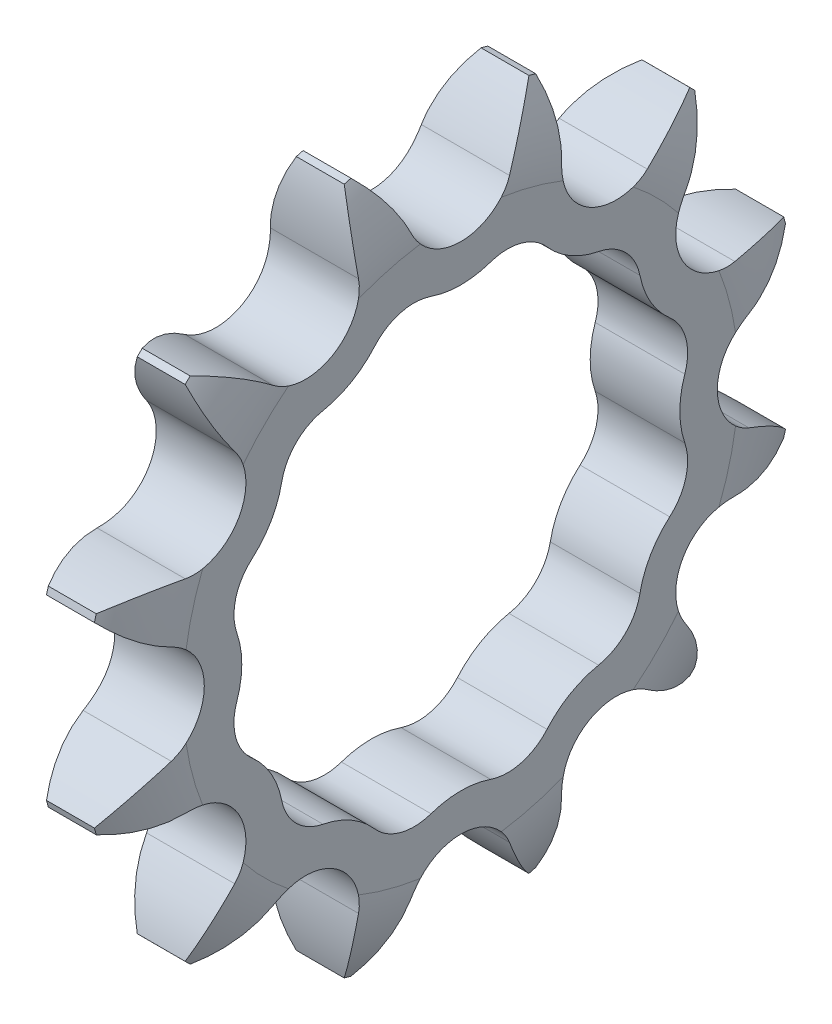
SolidWorks part; units mm, degrees
material "POM Acetal Copolymer"
ref_plane "Plane1" through (0, 0, 0) normal (0, 0, 1) x (1, 0, 0)
ref_plane "Plane2" through (0, 0, 0) normal (0, 1, 0) x (1, 0, 0)
ref_plane "Plane3" through (0, 0, 0) normal (1, 0, 0) x (0, 0, -1)
sketch "Clipboard" plane through (0, 0, 0) normal (0, 1, 0) x (1, 0, 0)
  line L0 (0, 0) -> (9.3169, -1.9804)
  line L1 (-15, 0) -> (100, 0) construction
  line L2 (0, 0) -> (-0.8203, 0.9272)
  line L3 (0, 0) -> (-8.8973, 3.4006)
  line L4 (0, 0) -> (3.0323, 0.6445)
  line L5 (0, 0) -> (-46.8476, -17.4728)
  line L6 (0, 0) -> (-4.4098, -2.9753)
  line L7 (-0.8203, 0.9272) -> (47.8986, 12.1748)
  line L8 (-76.2, 38.1) -> (-72.9, 38.1)
  line L9 (-73.3242, 40.7328) -> (-72.926, 40.7699)
  line L10 (-73.4529, 9.1872) -> (-63.2129, 9.1872)
  circle A0 centre (0, 0) radius 3.175
  circle A1 centre (0, 0) radius 13.0987
  circle A2 centre (0, 0) radius 37.5
  dimension "Dr" = 6.35
  dimension "MHD" = 26.1974
  dimension "Hub_dia" = 75
  dimension "Num_teeth" = 12
  dimension "Pitch" = 9.525
  dimension "Width" = 3.1
  dimension "Side_relief" = 1.238
  dimension "Side_radius" = 9.525
  dimension "Overall_len" = 50
  dimension "Show_teeth" = 12
  dimension "Thickness" = 5.3196
  dimension "OAL" = 50.0005
  dimension "T_dim" = 3.3
  dimension "Fillet_rad" = 0.4
  dimension "Face_width" = 5.32
  dimension "Num_strands" = 1
  dimension "Transv_pitch" = 10.24
  dimension "Plate_wid" = 8.26
sketch "BasProSke" plane through (0, 0, 0) normal (0, 1, 0) x (1, 0, 0)
  line L0 (-10, 0) -> (60, 0) construction
  line L1 (0, 0) -> (0, 16.4831)
  line L2 (0, 0) -> (5.3196, 0)
  line L3 (5.3196, 0) -> (5.3196, 16.4831)
  line L4 (4.0816, 21.179) -> (1.238, 21.179)
  arc A0 (0, 16.4831) -> (1.238, 21.179) centre (9.525, 16.4831) cw
  arc A1 (5.3196, 16.4831) -> (4.0816, 21.179) centre (-4.2054, 16.4831) ccw
  dimension "Thickness" = 5.3196
  dimension "D1" = 9.525
  dimension "G1" = 1.238
  dimension "G2" = 1.238
  dimension "Diameter" = 42.358
revolve "Base-Revolve" add sketch "BasProSke" angle 360 about L0
sketch "TooCutSke" plane through (0, 0, 0) normal (1, 0, 0) x (0, 0, -1)
  line L0 (0, 18.4326) -> (2.9352, 17.1411) construction
  line L1 (0, 0) -> (0, 107) construction
  line L2 (0, 18.4326) -> (-10, 18.4326) construction
  line L3 (0, 18.4326) -> (-2.9352, 17.1411) construction
  arc A0 (2.9352, 17.1411) -> (5.7185, 20.9112) centre (12.6997, 12.8446) cw
  arc A1 (2.9352, 17.1411) -> (-2.9352, 17.1411) centre (0, 18.4326) cw
  arc A2 (-2.9352, 17.1411) -> (-5.7185, 20.9112) centre (-12.6997, 12.8446) ccw
  arc A3 (5.7185, 20.9112) -> (-5.7185, 20.9112) centre (0, 0) ccw
  dimension "R1" = 3.2067
  dimension "R2" = 10.668
  dimension "Overcut" = 21.679
  dimension "Seat_radius" = 18.4326
  dimension "X" = 132.5
extrude "ToothCut" cut sketch "TooCutSke" along normal through all
pattern_circular "TeethCuts" count 12 every 30 about axis through (-10, 0, 0) along (1, 0, 0) of "ToothCut"
sketch "HubNeaOneSke" plane through (0, 0, 0) normal (-1, 0, 0) x (0, 0, 1)
  circle A0 centre (0, 0) radius 13.0987
  dimension "Diameter" = 26.1974
extrude "HubNearOne" [suppressed] add sketch "HubNeaOneSke" along normal blind 44.6809
fillet "HubNearOneFillet" [suppressed] radius 0.4
sketch "HubNeaBotSke" plane through (0, 0, 0) normal (-1, 0, 0) x (0, 0, 1)
  circle A0 centre (0, 0) radius 13.0987
  dimension "Diameter" = 26.1974
extrude "HubNearBoth" [suppressed] add sketch "HubNeaBotSke" along normal blind 22.3405
fillet "HubNearBothFillet" [suppressed] radius 0.4
ref_plane "FarPln" through (5.3196, 0, 0) normal (1, 0, 0) x (0, 0, -1)
sketch "HubFarSke" plane through (5.3196, 0, 0) normal (1, 0, 0) x (0, 0, -1)
  circle A0 centre (0, 0) radius 13.0987
  dimension "Diameter" = 26.1974
extrude "HubFar" [suppressed] add sketch "HubFarSke" along normal blind 22.3405
fillet "HubFarFillet" [suppressed] radius 0.4
sketch "BorSke" plane through (0, 0, 0) normal (1, 0, 0) x (0, 0, -1)
  circle A0 centre (0, 0) radius 13
  dimension "Diameter" = 26
extrude "Bore" cut sketch "BorSke" along normal mid plane 100.001
sketch "KeySke" plane through (0, 0, 0) normal (1, 0, 0) x (0, 0, -1)
  line L0 (-4, 0) -> (-4, 16.3)
  line L1 (-4, 16.3) -> (4, 16.3)
  line L2 (4, 16.3) -> (4, 0)
  line L3 (0, 0) -> (0, 34) construction
  line L4 (-4, 0) -> (4, 0)
  dimension "Offset" = 16.3
  dimension "Width" = 8
extrude "Keyway" [suppressed] cut sketch "KeySke" along normal mid plane 100.001
pattern_circular "Keyway2" [suppressed] count 2 every 90 about axis through (-10, 0, 0) along (1, 0, 0)
sketch "Sketch1" plane through (5.3196, 0, 0) normal (1, 0, 0) x (0, 0, -1)
  line L1 (-9.7794, 9.7794) -> (0, 0)
  line L2 (0, 0) -> (-13.359, 3.5795)
  arc A1 (-15.3232, 6.0741) -> (-12.9219, 10.2332) centre (-15.9631, 9.2163) ccw construction
  circle A2 centre (0, 0) radius 13 construction
  arc A3 (-12.3986, 5.1166) -> (-10.6304, 8.1792) centre (-15.9631, 9.2163) ccw
  arc A4 (-13.359, 3.5795) -> (-12.3986, 5.1166) centre (-10.3646, 2.7772) cw
  arc A5 (-10.6304, 8.1792) -> (-9.7794, 9.7794) centre (-7.5874, 7.5874) cw
  arc A6 (-14.8281, 15.1221) -> (-15.1221, 14.8281) centre (0, 0) ccw construction
  arc A7 (-20.4026, 5.6821) -> (-20.5102, 5.2804) centre (0, 0) ccw construction
  point P11 (-20.4574, 5.4815)
  point P17 (-14.9758, 14.9758)
  dimension "D1" = 3.1
extrude "Cut-Extrude1" cut sketch "Sketch1" against normal blind 10
pattern_circular "CirPattern1" count 12 over 360 about axis through (50.0005, 0, 0) along (-1, 0, 0) of "Cut-Extrude1"
equation "' \"Pitch@Clipboard\" = 12.7"
equation "' \"Num_strands@Clipboard\" = 1"
equation "' \"Num_teeth@Clipboard\" = 9"
equation "' \"Hub_dia@Clipboard\" = 50"
equation "' \"Overall_len@Clipboard\" = 3"
equation "' \"Diameter@BorSke\" = 12"
equation "' \"T_dim@Clipboard\" = 1"
equation "' \"Width@KeySke\" = 2"
equation "' \"Dr@Clipboard\" = 8.51"
equation "' \"Face_width@Clipboard\" = 7.2"
equation "' \"Side_radius@Clipboard\" = 12.7"
equation "' \"Side_relief@Clipboard\" = 1.27"
equation "' \"Transv_pitch@Clipboard\" = 13.92"
equation "' \"Show_teeth@Clipboard\" = 9"
equation "' \"Fillet_rad@Clipboard\" = 0.6"
equation "' \"Plate_wid@Clipboard\" = 11.8"
equation "\"Num_teeth@Clipboard\" = int( \"Num_teeth@Clipboard\" )"
equation "\"Num_teeth@Clipboard\" = ((sgn( \"Num_teeth@Clipboard\" - 5.0)+1)*( \"Num_teeth@Clipboard\" - 5.0))/2 +5.0"
equation "\"Num_teeth@Clipboard\" = ((sgn( \"Num_teeth@Clipboard\" - 200.0)-1)*( \"Num_teeth@Clipboard\" - 200.0))/-2 +200.0"
equation "\"MHD@Clipboard\" = \"Pitch@Clipboard\" * (1.0 / tan(3.14159265 / \"Num_teeth@Clipboard\" )) - 1.04 * \"Plate_wid@Clipboard\" - 0.76"
equation "\"Thickness@Clipboard\"  = \"Face_width@Clipboard\" + (\"Num_strands@Clipboard\" - 1) * \"Transv_pitch@Clipboard\""
equation "\"OAL@Clipboard\" = \"Thickness@Clipboard\" + 2 * \"Fillet_rad@Clipboard\" + 1"
equation "\"MHD@Clipboard\" = ((sgn( \"MHD@Clipboard\" - \"Hub_dia@Clipboard\" )-1)*( \"MHD@Clipboard\" - \"Hub_dia@Clipboard\" ))/-2+ \"Hub_dia@Clipboard\""
equation "\"OAL@Clipboard\" = ((sgn( \"OAL@Clipboard\" - \"Overall_len@Clipboard\" )+1)*( \"OAL@Clipboard\" - \"Overall_len@Clipboard\" ))/2 + \"Overall_len@Clipboard\" + 0.0005"
equation "\"Num_teeth@TeethCuts\" = int( \"Show_teeth@Clipboard\" ) + 1"
equation "\"Num_teeth@TeethCuts\" = ((sgn( \"Num_teeth@TeethCuts\" - \"Num_teeth@Clipboard\" )-1)*( \"Num_teeth@TeethCuts\" - \"Num_teeth@Clipboard\" ))/-2+ \"Num_teeth@Clipboard\""
equation "\"Num_teeth@TeethCuts\" = ((sgn( \"Num_teeth@TeethCuts\" - 2.0)+1)*( \"Num_teeth@TeethCuts\" - 2.0))/2 +2.0"
equation "\"Angle@TeethCuts\" = 360.0 / \"Num_teeth@Clipboard\""
equation "\"Seat_radius@TooCutSke\" = ( \"Pitch@Clipboard\" / 2.0) / sin(3.14159265 / \"Num_teeth@Clipboard\" ) - \"Dr@Clipboard\" / 2.0 + \"Dr@Clipboard\" * 0.505"
equation "\"R1@TooCutSke\"  = \"Dr@Clipboard\" * 0.505"
equation "\"X@TooCutSke\" = 140.0 - (90.0 / \"Num_teeth@Clipboard\")"
equation "\"R2@TooCutSke\" = 0.12 * \"Dr@Clipboard\" * ( \"Num_teeth@Clipboard\" + 2.0)"
equation "\"Overcut@TooCutSke\" = 0.5 + 0.625 * \"Pitch@Clipboard\" - 0.5 * \"Dr@Clipboard\"  +  \"Pitch@Clipboard\" / 2.0 / sin(3.14159265 / \"Num_teeth@Clipboard\" )"
equation "\"Diameter@BasProSke\" = 2.0 * ( 0.625 * \"Pitch@Clipboard\" - 0.5 * \"Dr@Clipboard\"  +  \"Pitch@Clipboard\" / 2.0 / sin(3.14159265 / \"Num_teeth@Clipboard\" ))"
equation "\"Thickness@BasProSke\"  = \"Thickness@Clipboard\""
equation "\"G1@BasProSke\" =  \"Side_relief@Clipboard\""
equation "\"G2@BasProSke\" =  \"Side_relief@Clipboard\""
equation "\"D1@BasProSke\" =  \"Side_radius@Clipboard\""
equation "\"Diameter@HubNeaOneSke\" = \"MHD@Clipboard\""
equation "\"Length@HubNearOne\" = \"OAL@Clipboard\" - \"Thickness@BasProSke\""
equation "\"Diameter@HubNeaBotSke\" = \"MHD@Clipboard\""
equation "\"Length@HubNearBoth\" = ( \"OAL@Clipboard\" - \"Thickness@BasProSke\" ) / 2.0"
equation "\"D1@HubNearOneFillet\" = \"Fillet_rad@Clipboard\""
equation "\"D1@HubNearBothFillet\" = \"Fillet_rad@Clipboard\""
equation "\"Thickness@FarPln\" = \"Thickness@BasProSke\""
equation "\"Diameter@HubFarSke\" = \"MHD@Clipboard\""
equation "\"Length@HubFar\" = ( \"OAL@Clipboard\" - \"Thickness@BasProSke\" ) / 2.0"
equation "\"D1@HubFarFillet\" = \"Fillet_rad@Clipboard\""
equation "\"D1@Bore\" = \"OAL@Clipboard\" * 2.0"
equation "\"D1@Keyway\" = \"OAL@Clipboard\" * 2.0"
equation "\"Offset@KeySke\" = \"T_dim@Clipboard\" + \"Diameter@BorSke\" / 2.0"
